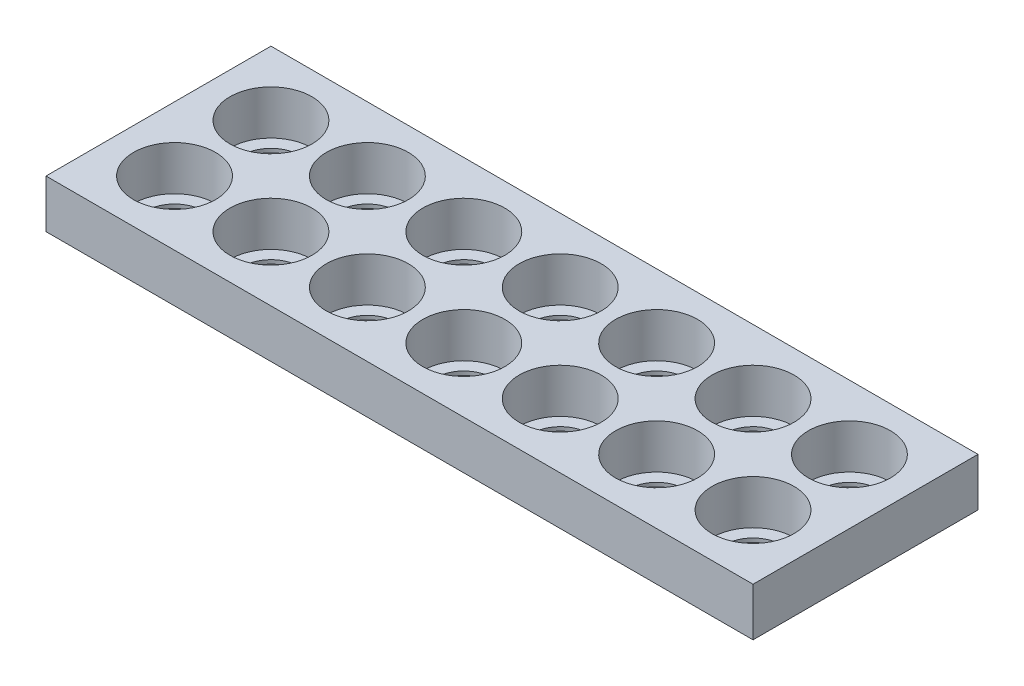
SolidWorks part; units mm, degrees
ref_plane "Front Plane" through (0, 0, 0) normal (0, 0, 1) x (1, 0, 0)
ref_plane "Top Plane" through (0, 0, 0) normal (0, 1, 0) x (1, 0, 0)
ref_plane "Right Plane" through (0, 0, 0) normal (1, 0, 0) x (0, 0, -1)
sketch "Sketch1" plane through (0, 0, 0) normal (0, 1, 0) x (1, 0, 0)
  line L1 (-16.9333, -16.9333) -> (169.3333, -16.9333)
  line L2 (-16.9333, -16.9333) -> (-16.9333, 42.3333)
  line L3 (-16.9333, 42.3333) -> (169.3333, 42.3333)
  line L4 (169.3333, -16.9333) -> (169.3333, 42.3333)
  circle A0 centre (0, 0) radius 10.8
  circle A1 centre (0, 0) radius 7.5
  circle A2 centre (25.4, 0) radius 10.8
  circle A3 centre (25.4, 0) radius 7.5
  circle A4 centre (50.8, 0) radius 10.8
  circle A5 centre (50.8, 0) radius 7.5
  circle A6 centre (76.2, 0) radius 10.8
  circle A7 centre (76.2, 0) radius 7.5
  circle A8 centre (101.6, 0) radius 10.8
  circle A9 centre (101.6, 0) radius 7.5
  circle A10 centre (127, 0) radius 10.8
  circle A11 centre (127, 0) radius 7.5
  circle A12 centre (152.4, 0) radius 10.8
  circle A13 centre (152.4, 0) radius 7.5
  circle A14 centre (25.4, 25.4) radius 10.8
  circle A15 centre (25.4, 25.4) radius 7.5
  circle A16 centre (50.8, 25.4) radius 10.8
  circle A17 centre (50.8, 25.4) radius 7.5
  circle A18 centre (76.2, 25.4) radius 10.8
  circle A19 centre (76.2, 25.4) radius 7.5
  circle A20 centre (101.6, 25.4) radius 10.8
  circle A21 centre (101.6, 25.4) radius 7.5
  circle A22 centre (127, 25.4) radius 10.8
  circle A23 centre (127, 25.4) radius 7.5
  circle A24 centre (152.4, 25.4) radius 10.8
  circle A25 centre (152.4, 25.4) radius 7.5
  circle A26 centre (0, 25.4) radius 10.8
  circle A27 centre (0, 25.4) radius 7.5
  dimension "D1" = 21.6
  dimension "D2" = 15
  dimension "D5" = 16.9333
  dimension "D7" = 16.9333
  dimension "D8" = 16.9333
  dimension "D6" = 16.9333
  dimension "D3" = 7
  dimension "D4" = 2
extrude "Boss-Extrude2" add sketch "Sketch1" along normal blind 12.7 contours L1 L4 L3 L2 A26 A24 A22 A20 A18 A16 A14 A12 A10 A8 A6 A4 A2 A0 region at (76.2, 0, -12.7)
extrude "Boss-Extrude3" add sketch "Sketch1<4>" along normal blind 1.016 contours A26 A27 | A14 A15 | A16 A17 | A18 A19 | A20 A21 | A22 A23 | A24 A25 | A0 A1 | A2 A3 | A4 A5 | A6 A7 | A8 A9 | A10 A11 | A12 A13 region at (-10.4945, 0, 0) region at (14.9055, 0, 0) region at (40.3055, 0, 0) region at (65.7055, 0, 0) region at (91.1055, 0, 0) region at (116.5055, 0, 0) region at (141.9055, 0, 0) region at (14.9055, 0, -25.4) region at (40.3055, 0, -25.4) region at (65.7055, 0, -25.4) region at (91.1055, 0, -25.4) region at (116.5055, 0, -25.4) region at (141.9055, 0, -25.4) region at (-10.4945, 0, -25.4)
sketch "Sketch1<4>" plane through (0, 0, 0) normal (0, 1, 0) x (1, 0, 0) same geometry as "Sketch1"
